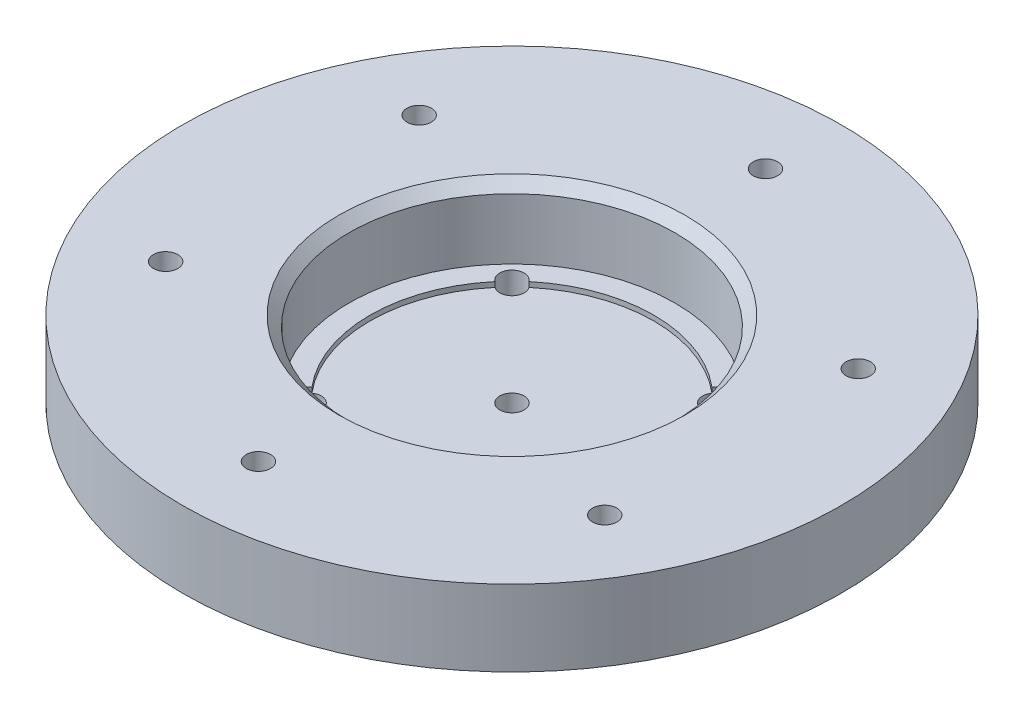
SolidWorks part; units mm, degrees
ref_plane "Ebene vorne" through (0, 0, 0) normal (0, 0, 1) x (1, 0, 0)
ref_plane "Ebene oben" through (0, 0, 0) normal (0, 1, 0) x (1, 0, 0)
ref_plane "Ebene rechts" through (0, 0, 0) normal (1, 0, 0) x (0, 0, -1)
sketch "Skizze1" plane through (0, 0, 0) normal (0, 0, 1) x (1, 0, 0)
  line L0 (0, 0) -> (0, -19560.6512) construction
  line L1 (0, 0) -> (20, 0)
  line L2 (20, 0) -> (20, 7.5)
  line L3 (20, 7.5) -> (32.5, 7.5)
  line L4 (32.5, 7.5) -> (32.5, 15)
  line L5 (32.5, 15) -> (16.075, 15)
  line L6 (16.075, 15) -> (16.075, 8)
  line L7 (14, 7.5) -> (0, 7.5)
  line L8 (0, 7.5) -> (0, 0)
  line L9 (14, 7.5) -> (14, 8)
  line L10 (14, 8) -> (16.075, 8)
  dimension "D1" = 40
  dimension "D2" = 65
  dimension "D3" = 15
  dimension "D4" = 7.5
  dimension "D5" = 32.15
  dimension "D6" = 0.5
  dimension "D7" = 28
revolve "Rotation1" add sketch "Skizze1" angle 360 about L0
hole_wizard "Ø2.4 (2.4) Durchmesser Bohrung1" positions "Skizze2" profile "Skizze3" hole size "Ø2.4" standard "ISO" end condition through all
sketch "Skizze2" plane through (0, 15, 0) normal (0, 1, 0) x (1, 0, 0)
  line L0 (0, 0) -> (0, -50000) construction
  point P5 (0, 25)
  dimension "D1" = 25
sketch "Skizze3" plane through (0, 15, -25) normal (1, 0, 0) x (0, 0, 1)
  line L0 (0, 0) -> (0, 15)
  line L1 (0, 15) -> (1.2, 15)
  line L2 (1.2, 15) -> (1.2, 0)
  line L5 (1.2, 0) -> (0, 0)
  line L11 (0, -6.35) -> (0, 107.95) construction
  dimension "Bohrerdurchmesser" = 2.4
  dimension "Bohrungstiefe" = 15
pattern_circular "Kreismuster1" count 6 over 360 about axis through (0, 15, 0) along (0, 1, 0) of "Ø2.4 (2.4) Durchmesser Bohrung1"
hole_wizard "Ø2.4 (2.4) Durchmesser Bohrung2" positions "Skizze4" profile "Skizze5" hole size "Ø2.4" standard "ISO" end condition through all
sketch "Skizze4" plane through (0, 0, 0) normal (0, -1, 0) x (-1, 0, 0)
  line L1 (-10, -10) -> (10, -10)
  line L2 (-10, -10) -> (-10, 10)
  line L3 (-10, 10) -> (10, 10)
  line L4 (10, -10) -> (10, 10)
  line L5 (-10, -10) -> (10, 10) construction
  line L6 (-10, 10) -> (10, -10) construction
  point P1 (0, 0)
  point P2 (10, 10)
  point P49 (-10, -10)
  point P50 (-10, 10)
  point P51 (10, -10)
  dimension "D1" = 20
  dimension "D2" = 20
sketch "Skizze5" plane through (0, 0, 0) normal (1, 0, 0) x (0, 0, -1)
  line L0 (0, 0) -> (0, 15)
  line L1 (0, 15) -> (1.2, 15)
  line L2 (1.2, 15) -> (1.2, 0)
  line L5 (1.2, 0) -> (0, 0)
  line L11 (0, -6.35) -> (0, 107.95) construction
  dimension "Bohrerdurchmesser" = 2.4
  dimension "Bohrungstiefe" = 15
chamfer "Fase1" distance 1 angle 45 1 edges at (0, 15, 16.075)
chamfer "Fase2" distance 1 angle 45 1 edges at (0, 0, 20)
